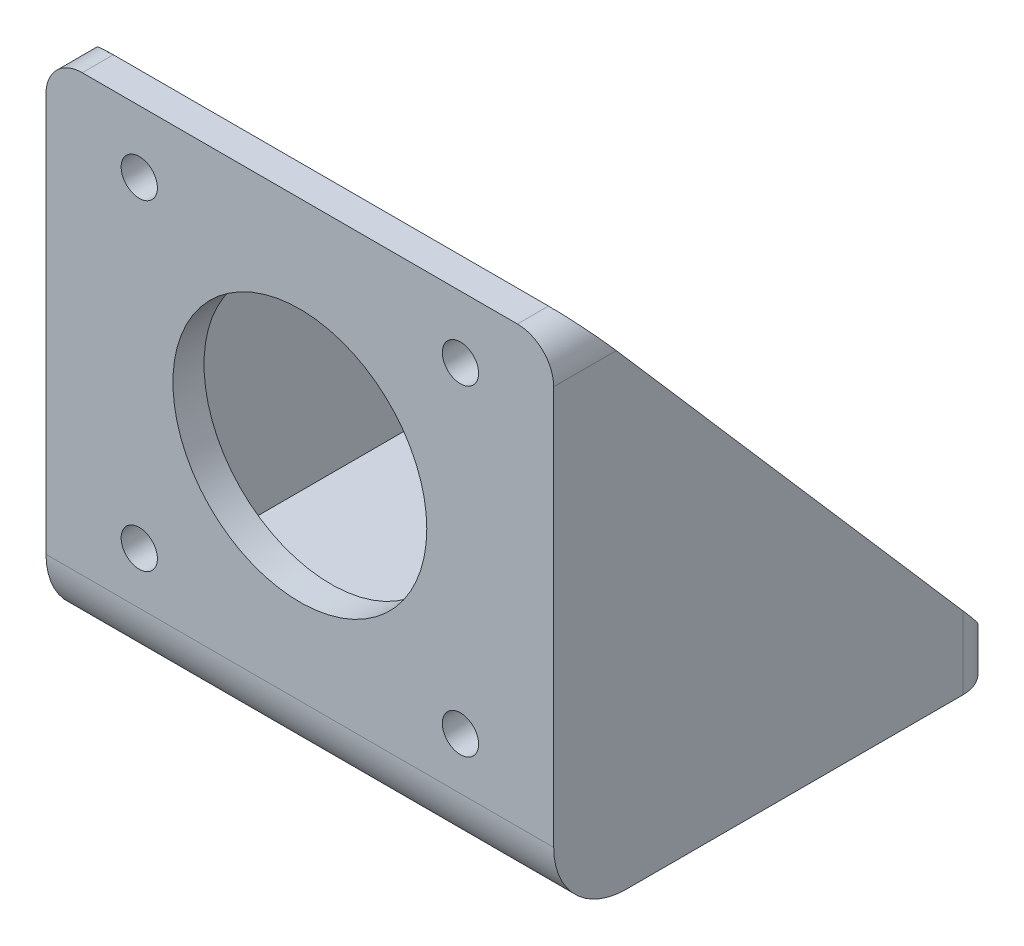
SolidWorks part; units mm, degrees
ref_plane "Plano frontal" through (0, 0, 0) normal (0, 0, 1) x (1, 0, 0)
ref_plane "Plano superior" through (0, 0, 0) normal (0, 1, 0) x (1, 0, 0)
ref_plane "Plano direito" through (0, 0, 0) normal (1, 0, 0) x (0, 0, -1)
sketch "Esboço1" plane through (0, 0, 0) normal (0, 1, 0) x (1, 0, 0)
  line L1 (-21.5, -21.5) -> (21.5, -21.5)
  line L2 (-21.5, -21.5) -> (-21.5, 21.5)
  line L3 (-21.5, 21.5) -> (21.5, 21.5)
  line L4 (21.5, -21.5) -> (21.5, 21.5)
  line L5 (-21.5, -21.5) -> (21.5, 21.5) construction
  line L6 (-21.5, 21.5) -> (21.5, -21.5) construction
  point P0 (0, 0)
  dimension "D1" = 43
  dimension "D2" = 43
extrude "Ressalto-extrusão1" add sketch "Esboço1" along normal blind 3
sketch "Esboço2" plane through (0, 3, 0) normal (0, 1, 0) x (1, 0, 0)
  line L0 (-21.5, -21.5) -> (-21.5, -18.5)
  line L1 (-21.5, 21.5) -> (-21.5, -21.5) construction
  line L2 (-21.5, -18.5) -> (21.5, -18.5)
  line L3 (21.5, -21.5) -> (21.5, 21.5) construction
  line L4 (21.5, -18.5) -> (21.5, -21.5)
  line L5 (21.5, -21.5) -> (-21.5, -21.5)
  dimension "D1" = 3
extrude "Ressalto-extrusão2" add sketch "Esboço2" along normal blind 46
sketch "Esboço3" plane through (0, 3, 0) normal (0, 1, 0) x (1, 0, 0)
  line L0 (0, 0) -> (14.945, 0) construction
  line L1 (0, 0) -> (0, 12.03) construction
  circle A0 centre (14.945, 12.03) radius 1.75
  circle A1 centre (14.945, -12.03) radius 1.75
  circle A2 centre (-14.945, -12.03) radius 1.75
  circle A3 centre (-14.945, 12.03) radius 1.75
  dimension "D3" = 3.5
  dimension "D1" = 12.03
  dimension "D2" = 14.945
  dimension "D4" = 14.945
  dimension "D5" = 12.03
extrude "Corte-extrusão1" cut sketch "Esboço3" against normal through all
sketch "Esboço4" plane through (0, 0, 21.5) normal (0, 0, 1) x (1, 0, 0)
  line L0 (-21.5, 49) -> (-21.5, 0) construction
  line L1 (-21.5, 49) -> (21.5, 49) construction
  line L4 (0, 0) -> (0, 49) construction
  line L5 (-21.5, 0) -> (21.5, 0) construction
  circle A0 centre (-15.5, 43) radius 1.75
  circle A1 centre (15.5, 43) radius 1.75
  circle A4 centre (-15.5, 12) radius 1.75
  circle A5 centre (15.5, 12) radius 1.75
  dimension "D3" = 3.5
  dimension "D1" = 6
  dimension "D2" = 6
  dimension "D4" = 12
  dimension "D5" = 6
extrude "Corte-extrusão2" cut sketch "Esboço4" against normal through all
sketch "Esboço5" plane through (-21.5, 0, 0) normal (-1, 0, 0) x (0, 0, 1)
  line L0 (-21.5, 0) -> (-21.5, 3)
  line L1 (-21.5, 3) -> (18.5, 49)
  line L2 (18.5, 49) -> (21.5, 49)
  line L3 (21.5, 49) -> (21.5, 0)
  line L4 (21.5, 0) -> (-21.5, 0)
extrude "Ressalto-extrusão3" add sketch "Esboço5" along normal blind 3
sketch "Esboço6" plane through (21.5, 0, 0) normal (1, 0, 0) x (0, 0, -1)
  line L0 (21.5, 0) -> (-21.5, 0)
  line L1 (-21.5, 0) -> (-21.5, 49)
  line L2 (-21.5, 49) -> (-18.5, 49)
  line L3 (-18.5, 49) -> (21.5, 3)
  line L4 (21.5, 3) -> (21.5, 0)
extrude "Ressalto-extrusão4" add sketch "Esboço6" along normal blind 3
sketch "Esboço7" plane through (0, 0, 21.5) normal (0, 0, 1) x (1, 0, 0)
  line L0 (-15.5, 43) -> (15.5, 12) construction
  circle A0 centre (0, 27.5) radius 12.25
  dimension "D1" = 24.5
extrude "Corte-extrusão3" cut sketch "Esboço7" against normal blind 3
fillet "Filete1" radius 3.5 2 edges at (-24.5, 49, 20) (24.5, 49, 20)
fillet "Filete2" radius 7 1 edges at (0, 0, 21.5)
fillet "Filete3" radius 3.5 2 edges at (-24.5, 1.5, -21.5) (24.5, 1.5, -21.5)
fillet "Filete4" radius 5 1 edges at (0, 3, 18.5)
sketch "Esboço8" plane through (0, 3, 0) normal (0, 1, 0) x (1, 0, 0)
  line L0 (0, 0) -> (0, 21.5) construction
  line L1 (21, 21.5) -> (-21, 21.5) construction
  line L2 (-8, 13.5) -> (8, 13.5)
  line L3 (-8, 13.5) -> (-8, 21.5)
  line L4 (-8, 21.5) -> (8, 21.5)
  line L5 (8, 21.5) -> (8, 13.5)
  point P8 (0, 13.5)
  dimension "D1" = 8
  dimension "D2" = 16
extrude "Corte-extrusão4" cut sketch "Esboço8" against normal through all
fillet "Filete5" radius 1 4 edges at (8, 1.5, -21.5) (8, 1.5, -13.5) (-8, 1.5, -13.5) (-8, 1.5, -21.5)
